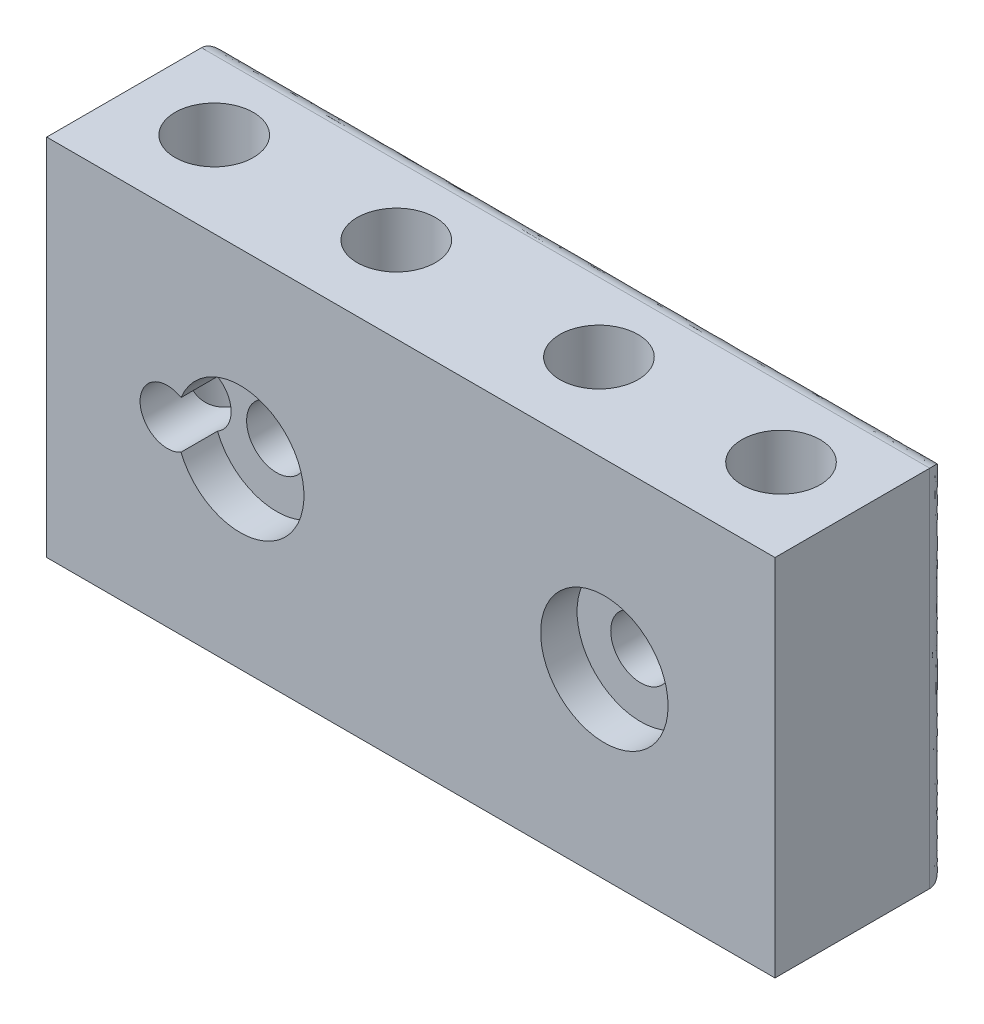
SolidWorks part; units mm, degrees
material "petg 20%"
ref_plane "Front Plane" through (0, 0, 0) normal (0, 0, 1) x (1, 0, 0)
ref_plane "Top Plane" through (0, 0, 0) normal (0, 1, 0) x (1, 0, 0)
ref_plane "Right Plane" through (0, 0, 0) normal (1, 0, 0) x (0, 0, -1)
sketch "Sketch1" plane through (0, 0, 0) normal (0, 0, 1) x (1, 0, 0)
  line L1 (20, 10) -> (-20, 10)
  line L2 (20, 10) -> (20, -10)
  line L3 (20, -10) -> (-20, -10)
  line L4 (-20, 10) -> (-20, -10)
  line L5 (20, 10) -> (-20, -10) construction
  line L6 (20, -10) -> (-20, 10) construction
  point P0 (0, 0)
  dimension "D1" = 40
  dimension "D2" = 20
extrude "Boss-Extrude1" add sketch "Sketch1" along normal blind 9.5
sketch "Sketch3" plane through (0, 0, 0) normal (0, 0, -1) x (-1, 0, 0)
  line L0 (13.3714, -3.45) -> (1.3714, -3.45)
  line L1 (13.3714, 3.45) -> (1.3714, 3.45)
  line L2 (-10.6286, 0) -> (9.9214, 0) construction
  arc A0 (-6.4266, 6.3327) -> (-6.4266, -6.3327) centre (-10.6286, 0) ccw
  arc A1 (13.3714, -3.45) -> (13.3714, 3.45) centre (13.3714, 0) ccw
  spline S0 degree 2 poles (-6.4266, -6.3327) (-3.0128, -3.5547) (1.3714, -3.45) knots 0 0 0 1 1 1
  spline S1 degree 2 poles (-6.4266, 6.3327) (-3.0128, 3.5547) (1.3714, 3.45) knots 0 0 0 1 1 1
  dimension "D1" = 15.2
  dimension "D2" = 6.9
extrude "Cut-Extrude1" cut sketch "Sketch3" against normal blind 2
fillet "Fillet1" radius 1 4 edges at (-20, 0, 0) (0, -10, 0) (0, 10, 0) (20, 0, 0) first distance on face at (-1.3801, -0.4805, 0)
sketch "Sketch4" plane through (0, 10, 0) normal (0, 1, 0) x (1, 0, 0)
  line L0 (20, -9.5) -> (20, -1) construction
  circle A0 centre (-15.5, -4.8) radius 2.15
  circle A1 centre (-5.5, -4.8) radius 2.15
  circle A2 centre (5.63, -4.8) radius 2.15
  circle A3 centre (15.63, -4.8) radius 2.15
  dimension "D1" = 4.3
  dimension "D2" = 4.3
  dimension "D3" = 4.3
  dimension "D4" = 4.3
  dimension "D5" = 4.37
  dimension "D6" = 14.37
extrude "Cut-Extrude2" cut sketch "Sketch4" against normal through all
sketch "Sketch5" plane through (0, 0, 0) normal (0, 0, -1) x (-1, 0, 0)
  circle A0 centre (13.3714, 0) radius 1.5
  circle A1 centre (9.3714, 0) radius 1.65
  circle A2 centre (-10.6286, 0) radius 1.65
  dimension "D1" = 3.3
  dimension "D2" = 3
  dimension "D3" = 4
  dimension "D4" = 3.3
extrude "Cut-Extrude3" cut sketch "Sketch5" against normal through all
sketch "Sketch6" plane through (0, 0, 9.5) normal (0, 0, 1) x (1, 0, 0)
  circle A0 centre (10.6286, 0) radius 3.5
  circle A1 centre (-9.3714, 0) radius 3.5
  dimension "D1" = 7
  dimension "D2" = 7
extrude "Cut-Extrude4" cut sketch "Sketch6" against normal blind 2
